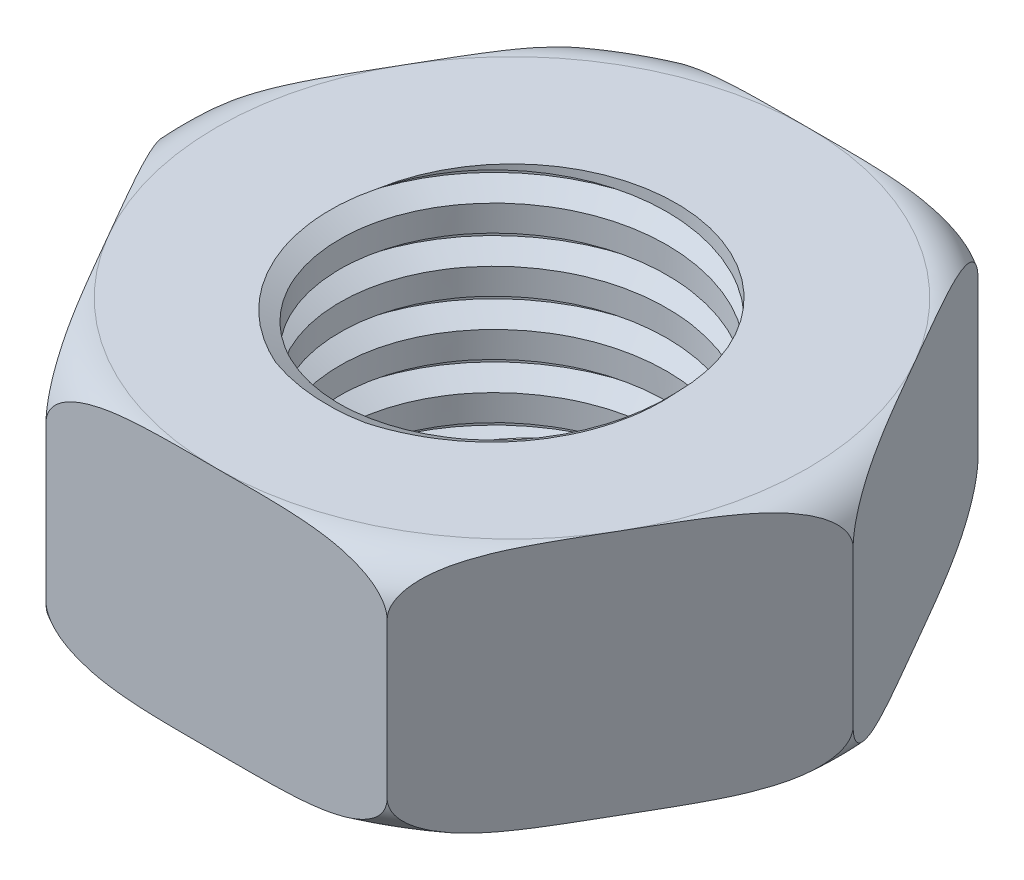
SolidWorks part; units mm, degrees
ref_plane "Front Plane" through (0, 0, 0) normal (0, 0, 1) x (1, 0, 0)
ref_plane "Top Plane" through (0, 0, 0) normal (0, 1, 0) x (1, 0, 0)
ref_plane "Right Plane" through (0, 0, 0) normal (1, 0, 0) x (0, 0, -1)
sketch "Sketch1" plane through (0, 0, 0) normal (0, 1, 0) x (1, 0, 0)
  line L1 (3.1177, 0) -> (1.5588, 2.7)
  line L2 (1.5588, 2.7) -> (-1.5588, 2.7)
  line L3 (-1.5588, 2.7) -> (-3.1177, 0)
  line L4 (-3.1177, 0) -> (-1.5588, -2.7)
  line L5 (-1.5588, -2.7) -> (1.5588, -2.7)
  line L6 (1.5588, -2.7) -> (3.1177, 0)
  circle A0 centre (0, 0) radius 2.7 construction
  circle A1 centre (0, 0) radius 1.5
  dimension "D2" = 3
  dimension "D1" = 5.4
extrude "Boss-Extrude1" add sketch "Sketch1" along normal mid plane 2.25
sketch "Sketch2" plane through (0, 0, 0) normal (0, 0, 1) x (1, 0, 0)
  line L0 (0, 1.125) -> (0, 0) construction
  line L3 (3.1177, 1.125) -> (3.1177, 0.7073)
  line L4 (1.5588, 1.125) -> (3.1177, 1.125) construction
  line L5 (3.1177, 1.125) -> (3.1177, -1.125) construction
  line L6 (1.5588, -1.125) -> (3.1177, -1.125) construction
  line L7 (2.7, -1.125) -> (3.1177, -1.125)
  line L8 (3.1177, -0.7073) -> (3.1177, -1.125)
  line L9 (3.1177, 1.125) -> (2.7, 1.125)
  line L10 (0, 1.125) -> (2.7, 1.125) construction
  arc A0 (2.7, 1.125) -> (3.1177, 0.7073) centre (2.7, 0.7073) cw
  arc A1 (3.1177, -0.7073) -> (2.7, -1.125) centre (2.7, -0.7073) cw
  dimension "D1" = 2.7
revolve "Cut-Revolve1" cut sketch "Sketch2" angle 360 about L0
thread "Thread1" pitch 0.35 start angle 0, offset 0, length 10, pitch 0.5, diameter 3
ref_plane "Plane1" through (1.5, 1.125, 0) normal (0, 0, 1) x (1, 0, 0)
sketch "Thread Profile1" plane through (1.5, 1.125, 0) normal (0, 0, 1) x (1, 0, 0)
  line L0 (0, 0) -> (0, 0.35) construction
  line L1 (0, 0) -> (0.1894, 0.1094)
  line L2 (0.1894, 0.1094) -> (0.1894, 0.1531)
  line L3 (0.1894, 0.1531) -> (0, 0.2625)
  line L4 (0.1894, 0.1312) -> (0, 0.1312) construction
  line L11 (0, 0) -> (0, 0.2625)
  point P2 (0, 0)
  dimension "Pitch" = 0.35
  dimension "Profile_Angle" = 60
  dimension "Profile_Land" = 0.0437
  dimension "Profile_Height" = 0.1894
